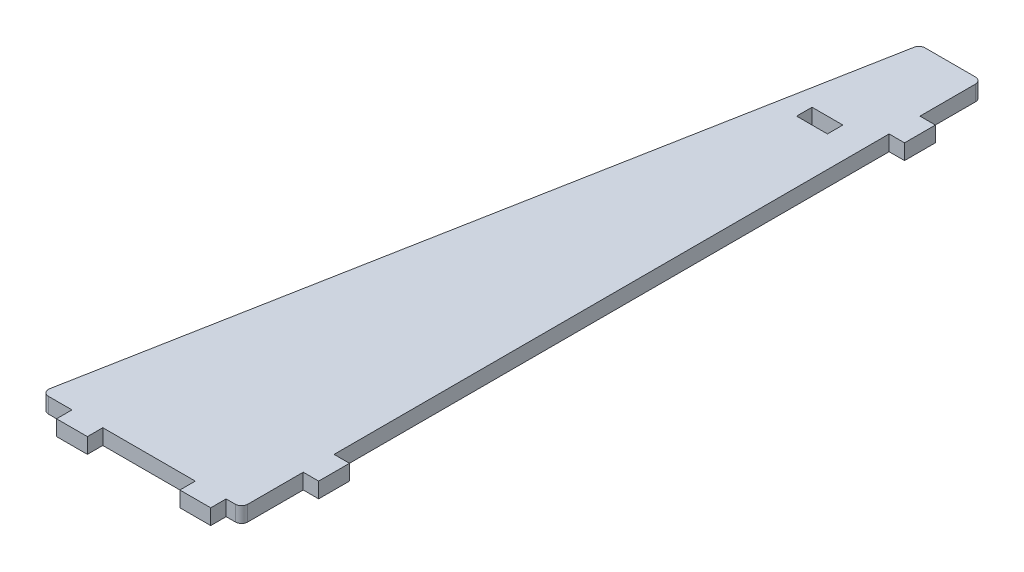
SolidWorks part; units mm, degrees
material "Beech"
ref_plane "Front Plane" through (0, 0, 0) normal (0, 0, 1) x (1, 0, 0)
ref_plane "Top Plane" through (0, 0, 0) normal (0, 1, 0) x (1, 0, 0)
ref_plane "Right Plane" through (0, 0, 0) normal (1, 0, 0) x (0, 0, -1)
sketch "Sketch1" plane through (0, 0, 0) normal (0, 1, 0) x (1, 0, 0)
  line L0 (0, 0) -> (12.7, 0)
  line L1 (12.7, 0) -> (12.7, -6.35)
  line L2 (12.7, -6.35) -> (25.4, -6.35)
  line L3 (25.4, -6.35) -> (25.4, 0)
  line L4 (25.4, 0) -> (63.5, 0)
  line L5 (63.5, 0) -> (63.5, -6.35)
  line L6 (63.5, -6.35) -> (76.2, -6.35)
  line L7 (76.2, -6.35) -> (76.2, 0)
  line L8 (76.2, 0) -> (82.55, 0)
  line L9 (82.55, 0) -> (82.55, 25.4)
  line L10 (82.55, 304.8) -> (57.15, 304.8)
  line L11 (57.15, 304.8) -> (0, 0)
  line L12 (82.55, 25.4) -> (88.9, 25.4)
  line L13 (88.9, 25.4) -> (88.9, 38.1)
  line L14 (88.9, 38.1) -> (82.55, 38.1)
  line L15 (82.55, 38.1) -> (82.55, 266.7)
  line L16 (82.55, 266.7) -> (88.9, 266.7)
  line L17 (88.9, 266.7) -> (88.9, 279.4)
  line L18 (88.9, 279.4) -> (82.55, 279.4)
  line L19 (82.55, 279.4) -> (82.55, 304.8)
  line L20 (57.15, 260.35) -> (57.15, 254)
  line L21 (57.15, 260.35) -> (69.85, 260.35)
  line L22 (57.15, 254) -> (69.85, 254)
  line L23 (69.85, 260.35) -> (69.85, 254)
  dimension "D1" = 12.7
  dimension "D2" = 6.35
  dimension "D3" = 25.4
  dimension "D4" = 50.8
  dimension "D5" = 12.7
  dimension "D6" = 304.8
  dimension "D7" = 25.4
  dimension "D8" = 25.4
  dimension "D9" = 6.35
  dimension "D10" = 254
  dimension "D11" = 6.35
  dimension "D12" = 12.7
  dimension "D13" = 12.7
extrude "Boss-Extrude1" add sketch "Sketch1" along normal blind 6.35
fillet "Fillet1" radius 2.54 4 edges at (82.55, 3.175, 0) (82.55, 3.175, -304.8) (57.15, 3.175, -304.8) (0, 3.175, 0)
equation "\"CageLeftBottomEdge\"=22.11mm"
equation "\"CageLeftTopEdge\"=22.11mm"
equation "\"CageRightBottomEdge\"=21.63mm"
equation "\"CageRightTopEdge\"=21.63mm"
equation "\"CageHeight\"=86.04mm"
equation "\"CageLength\"=73.76mm"
equation "\"CageTopScrewClearance\"=10mm"
equation "\"CageBottomScrewClearance\"=25mm"
equation "\"CageLeftTopDepth\"= 11.65mm"
equation "\"CageLeftBottomDepth\"=11.11mm"
equation "\"CageLeftTopHeight\"=8.56175mm"
equation "\"CageLeftBottomHeight\"=16mm"
equation "\"CageRightTopDepth\"= 11.05mm"
equation "\"CageRightBottomDepth\"=10.58mm"
equation "\"CageRightTopHeight\"=9.6mm"
equation "\"CageRightBottomHeight\"=15.49mm"
equation "\"CageLeftTopChannelDepth\"=2.41908mm"
equation "\"CageLeftBottomChannelDepth\"=2.588mm"
equation "\"CageLeftChannelHeight\"=11.7mm"
equation "\"CageRightTopChannelDepth\"=2.32mm"
equation "\"CageRightBottomChannelDepth\"=2.318mm"
equation "\"CageRightChannelHeight\"=10mm"
equation "\"CageChanRelHeight\"=23.99mm"
equation "\"CageChanRelDepth\"=5.492mm"
equation "\"CageChamberRadius\"=16.261mm"
equation "\"CageScrewDiameter\"=4.8mm"
equation "\"CageSetScrewDiameter\"=3.5mm"
equation "\"CageAxleRadius\"=6.639mm"
equation "\"CageAxleKeyHeight\"=1.619mm"
equation "\"CageAxleKeyWidth\"=2.662mm"
equation "\"CageHoseWindowWidth\"=16.29mm"
equation "\"CageHoseWindowHeight\"=26.5mm"
equation "\"CageHoseWindow-Edge\"=8.89mm"
equation "\"CageScrew-VerticalEdge\"=5.0mm"
equation "\"CageScrew-HorizontalEdge\"=7.5mm"
equation "\"CageScrew-HoseCornerScrewEdge\"=4.45mm"
equation "\"CageAxle-BottomEdge\"=56.05mm"
equation "\"CageAxle-FrontEdge\"=46.03mm"
equation "\"CageBackSetScrew-Axle\"=40mm"
equation "\"CageFrontSetScrew-Axle\"=22mm"
equation "\"CageVelocityWindow-BackEdge\"=34.8mm"
equation "\"CageVelocityWindow-BottomEdge\"=27.55mm"
equation "\"CageVelocityWindowHeight\"=22.29mm"
equation "\"CageVelocityWindowWidth\"=12.61mm"
equation "\"TriggerSlot-BottomEdge\"=6.35mm"
equation "\"TriggerSlot-FrontEdge\"=15mm"
equation "\"TriggerSlotSize\"=6.7mm"
equation "\"TriggerRackOffset\"=.236224in"
equation "\"TriggerSlotSizeInt\"=.25in"
equation "\"MotorMountLegLength\"=.25in"
equation "\"GearOffset\"=.264907in"
equation "\"TriggerSlotSpacing\"=.25in"
equation "\"TriggerMiniSlotWidth\"=3.5mm"
equation "\"TriggerRackWidth\"=6.5mm"
equation "\"TGMGearFaceDiameter\"=24.40mm"
equation "\"TGMCylinderLength\"=15.00mm"
equation "\"TGMScrewHole-Center\"=8.70mm"
equation "\"TGMScrewHoleDiameter\"=5.04mm"
equation "\"TGMCenterHoleDiameter\"=9.50mm"
equation "\"TGMShaftCollarSideLength\"=19.00mm"
equation "\"TGMShaftCollarDockingDepth\"=7.00mm"
equation "\"whitemotordepth\"=11.27mm"
equation "\"whitemotorbackdepth\"=3.845mm"
equation "\"whitemotoraxledepth\" = 3.5mm"
equation "\"whitemotoraxleoffset\"=11.4mm"
equation "\"whitemotorwidth\"=12.07mm"
equation "\"whitemotorheight\"=16.68mm"
equation "\"whitemotorcylinderlength\" =13.04mm"
equation "\"whitemotorcylinderradius\"=3.845mm"
equation "\"whitemotorcylinderoffset\"=2.35mm"
equation "\"whitemotorcutoutlength\"=1.88mm"
equation "\"whitemotorouterrad\"=5mm"
equation "\"whitemotorinnerrad\"=2.95mm"
equation "\"elasticracklength\"=2in"
equation "\"elasticrackpegsize\"=.25in"
equation "\"elasticrackpegbuffer\"=.125in"
equation "\"elasticrackpegspacing\"=1.76476378in"
equation "\"elasticbaybuffer\"=.25in"
equation "\"elasticdepth\"=.125in"
equation "\"elasticbaydepth\"=.75in"
equation "\"motormountwidth\"=12mm"
equation "\"motormountcornerfillet\"=3mm"
equation "\"pandiscradius\"=14in"
equation "\"towermaterialwidth\"=.25in"
equation "\"towerslotlength\"=.5in"
equation "\"towermarkerspace\"=5in"
equation "\"towerslothorizoffset\"=1in"
equation "\"towerslothorizspacing\"=2in"
equation "\"towerslotvertoffset\"=3in"
equation "\"D1@Sketch1\"=\"towerslotlength\""
equation "\"D2@Sketch1\"=\"towermaterialwidth\""
equation "\"towerupslot\"=1in"
equation "\"D3@Sketch1\"=\"towerupslot\""
equation "\"towerslotvertspacing\"=2in"
equation "\"D4@Sketch1\"=\"towerslotvertspacing\""
equation "\"D5@Sketch1\"=\"towerslotlength\""
equation "\"towerheight\"=12in"
equation "\"D6@Sketch1\"=\"towerheight\""
equation "\"D7@Sketch1\"=\"towerslotlength\"*2"
equation "\"D8@Sketch1\"=\"towerupslot\""
equation "\"D9@Sketch1\"=\"towerslotvertoffset\"-(\"towermarkerspace\"/2)-\"towermaterialwidth\""
equation "\"towermotorpanelheight\"=10in"
equation "\"D10@Sketch1\"=\"towermotorpanelheight\""
equation "\"D11@Sketch1\"=\"towermaterialwidth\""
equation "\"D12@Sketch1\"=\"towerslotlength\""
equation "\"D13@Sketch1\"=\"towerslotlength\""
equation "\"D1@Boss-Extrude1\"=\"towermaterialwidth\""
equation "\"toweraxle\"=.5in"
equation "\"towerplatslotoffset\"=1.5in"
equation "\"towerplatdepth\"=2in"
equation "\"stepperouterrad\"=10mm"
equation "\"stepperscrewsize\"=3.45mm"
equation "\"stepperscrewc2c\"=49.5mm"
equation "\"stepperdepthoffset\"=24mm"
equation "\"stepperhorizoffset\"=22.91mm"
